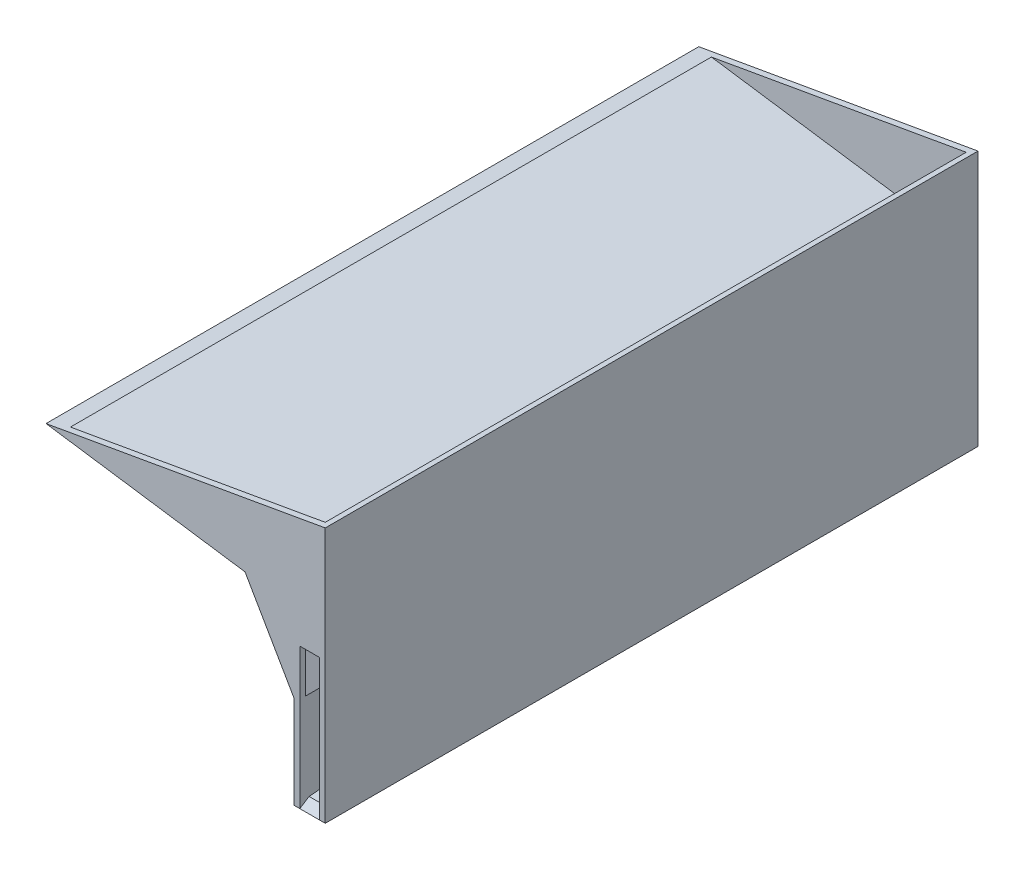
SolidWorks part; units mm, degrees
ref_plane "Front Plane" through (0, 0, 0) normal (0, 0, 1) x (1, 0, 0)
ref_plane "Top Plane" through (0, 0, 0) normal (0, 1, 0) x (1, 0, 0)
ref_plane "Right Plane" through (0, 0, 0) normal (1, 0, 0) x (0, 0, -1)
sketch "Sketch2" plane through (0, 0, 0) normal (0, 0, 1) x (1, 0, 0)
  line L0 (0, 0) -> (-105, 181.8653)
  line L1 (-105, 181.8653) -> (-532.9388, 244.1441)
  line L2 (-532.9388, 244.1441) -> (67.4, 350)
  line L3 (67.4, 350) -> (67.4, -200)
  line L4 (67.4, -200) -> (0, -200)
  line L5 (0, -200) -> (0, 0)
  dimension "D1" = 150
  dimension "D2" = 609.6
  dimension "D3" = 550
  dimension "D4" = 200
  dimension "D5" = 67.4
  dimension "D6" = 210
  dimension "D7" = 280
extrude "Boss-Extrude1" add sketch "Sketch2" along normal mid plane 1403.35
shell "Shell1" thickness 12.7
sketch "Sketch3" plane through (0, 0, 701.675) normal (0, 0, 1) x (1, 0, 0)
  line L1 (12.7, -187.3) -> (54.7, -187.3)
  line L2 (12.7, -187.3) -> (12.7, 102.7)
  line L3 (12.7, 102.7) -> (54.7, 102.7)
  line L4 (54.7, -187.3) -> (54.7, 102.7)
  line L6 (0, -200) -> (67.4, -200) construction
  point P6 (33.7, -200)
  point P7 (33.7, -187.3)
  dimension "D1" = 42
  dimension "D2" = 12.7
  dimension "D3" = 290
extrude "Cut-Extrude1" cut sketch "Sketch3" against normal blind 20
sketch "Sketch4" plane through (12.7, 0, 0) normal (1, 0, 0) x (0, 0, -1)
  line L0 (688.975, -187.3) -> (688.975, -67.3837)
  line L1 (688.975, -67.3837) -> (-681.675, -187.3)
  line L2 (-681.675, -187.3) -> (688.975, -187.3)
  line L3 (701.675, -200) -> (701.675, 350) construction
  line L4 (-701.675, -200) -> (701.675, -200) construction
  line L5 (-701.675, -200) -> (-701.675, 350) construction
  dimension "D1" = 12.7
  dimension "D2" = 12.7
  dimension "D3" = 20
  dimension "D4" = 5
extrude "Boss-Extrude2" add sketch "Sketch4" along normal up to surface (42 mm away)
chamfer "Chamfer1" distance 12.7 distance2 20 3 edges at (12.7, -187.3, 691.675) (54.7, -187.3, 691.675) (33.7, -187.3, 701.675)
scale "Scale1" [suppressed]
sketch "Sketch6" plane through (0, 0, 701.675) normal (0, 0, 1) x (1, 0, 0)
  line L1 (-167.2364, 157.2102) -> (-3.283, 157.2102)
  line L2 (-167.2364, 157.2102) -> (-167.2364, -5.4179)
  line L3 (-167.2364, -5.4179) -> (-3.283, -5.4179)
  line L4 (-3.283, 157.2102) -> (-3.283, -5.4179)
extrude "Cut-Extrude3" [suppressed] cut sketch "Sketch6" against normal blind 200
